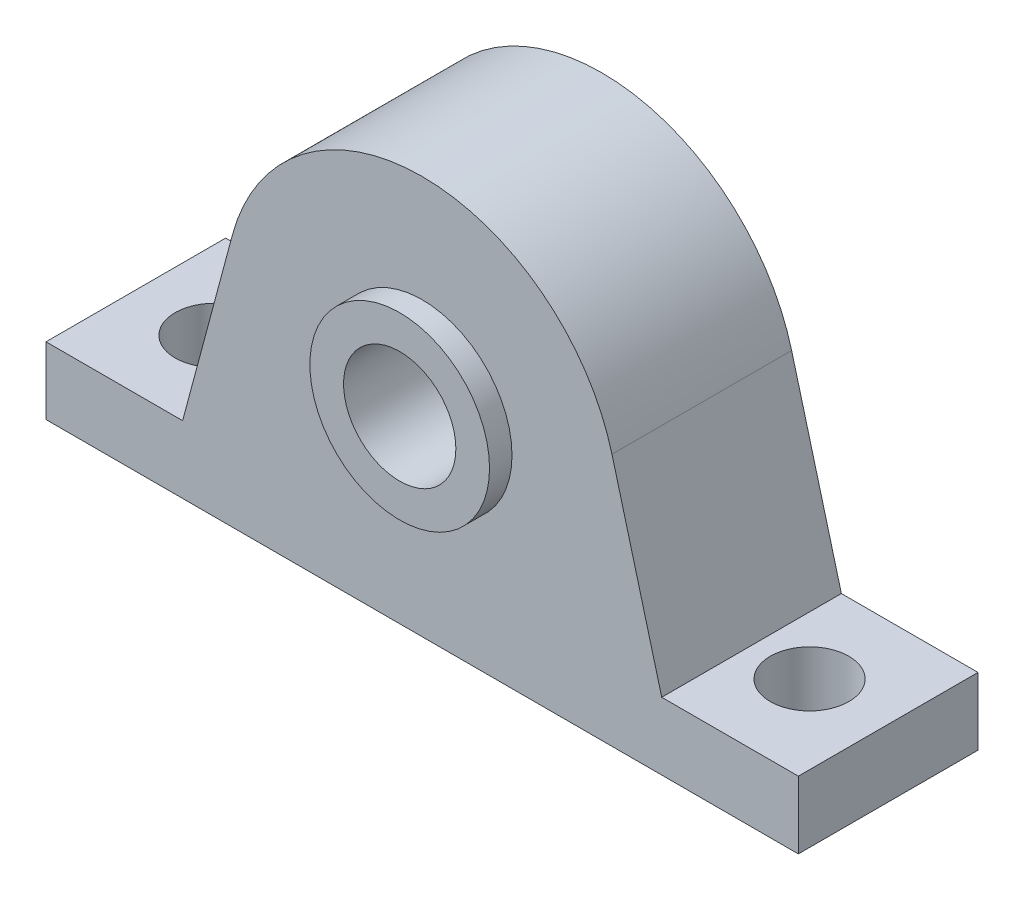
SolidWorks part; units mm, degrees
ref_plane "前视基准面" through (0, 0, 0) normal (0, 0, 1) x (1, 0, 0)
ref_plane "上视基准面" through (0, 0, 0) normal (0, 1, 0) x (1, 0, 0)
ref_plane "右视基准面" through (0, 0, 0) normal (1, 0, 0) x (0, 0, -1)
sketch "草图1" plane through (0, 0, 0) normal (0, 0, 1) x (1, 0, 0)
  line L0 (-33.1707, 0) -> (31.7073, 0) construction
  line L1 (0, 28.7317) -> (0, -23.1707) construction
  line L2 (-33.5, 0) -> (-33.5, 6)
  line L3 (-33.5, 6) -> (-21.3327, 6)
  line L4 (-33.5, 0) -> (33.5, 0)
  line L5 (-21.3327, 6) -> (-16.9037, 22.5293)
  line L6 (33.5, 0) -> (33.5, 6)
  line L7 (21.3327, 6) -> (16.9037, 22.5293)
  line L8 (33.5, 6) -> (21.3327, 6)
  circle A0 centre (0, 18) radius 17.5
  circle A1 centre (0, 18) radius 5
  point P13 (0, 0)
  dimension "D2" = 10
  dimension "D5" = 35
  dimension "D1" = 18
  dimension "D3" = 6
  dimension "D4" = 67
  dimension "D6" = 75
extrude "凸台-拉伸1" add sketch "草图1" along normal blind 16 contours A0 L5 L3 L2 L4 L6 L8 L7 | A0 A1 region at (-32.7931, 3, 0) region at (0, 35.005, 0)
sketch "草图2" plane through (0, 0, 16) normal (0, 0, 1) x (1, 0, 0)
  circle A0 centre (0, 18) radius 8
  circle A1 centre (0, 18) radius 5 construction
  circle A2 centre (0, 18) radius 5
  dimension "D1" = 16
extrude "凸台-拉伸2" add sketch "草图2" along normal blind 2
sketch "草图3" plane through (0, 6, 0) normal (0, 1, 0) x (1, 0, 0)
  line L0 (-33.5, -8) -> (33.5, -8) construction
  line L1 (-33.5, -16) -> (-33.5, 0) construction
  line L2 (33.5, -16) -> (33.5, 0) construction
  line L3 (0, 0) -> (0, -36.7743) construction
  circle A0 centre (-26.5, -8) radius 3.5
  circle A1 centre (26.5, -8) radius 3.5
  dimension "D1" = 7
  dimension "D2" = 53
extrude "切除-拉伸1" cut sketch "草图3" against normal blind 12
